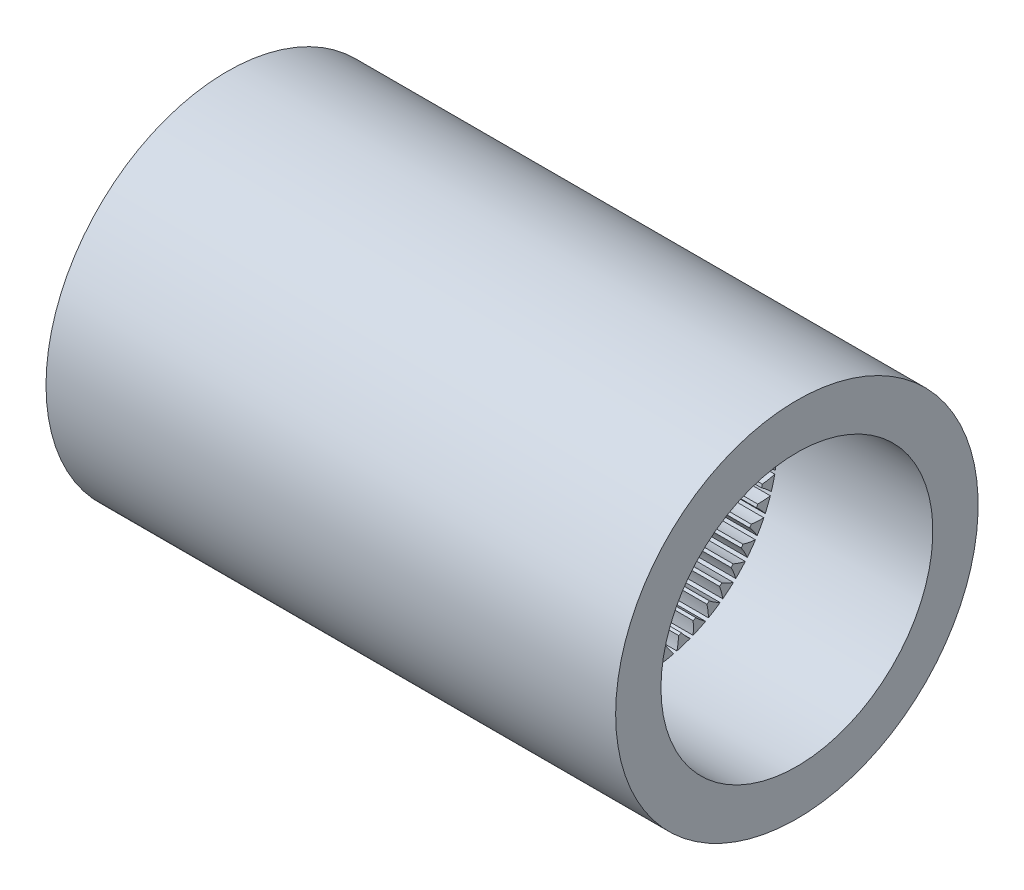
SolidWorks part; units mm, degrees
ref_plane "Plane1" through (0, 0, 0) normal (0, 0, 1) x (1, 0, 0)
ref_plane "Plane2" through (0, 0, 0) normal (0, 1, 0) x (1, 0, 0)
ref_plane "Plane3" through (0, 0, 0) normal (1, 0, 0) x (0, 0, -1)
other "Configuration Table"
sketch "HoldingSke" plane through (0, 0, 0) normal (0, 1, 0) x (1, 0, 0)
  line L0 (0, 0) -> (1.2856, -1.5321)
  line L1 (-15, 0) -> (100, 0) construction
  line L2 (0, 0) -> (-2.1039, 2.3779)
  line L3 (0, 0) -> (-11.863, 4.5341)
  line L4 (0, 0) -> (5.5511, 6.6156)
  line L5 (0, 0) -> (-23.7986, -8.8762)
  line L6 (0, 0) -> (-10.5278, -7.1032)
  line L7 (-2.1039, 2.3779) -> (3.3635, 27.1825)
  line L8 (-76.2, 2.8779) -> (-54.61, 2.8779)
  line L9 (-71.009, 38.7566) -> (-53.1078, 45.2721)
  line L10 (-76.2, 71.12) -> (104.1128, 71.12)
  line L11 (0, 0) -> (-15, 0)
  line L12 (-76.2, 101.6) -> (-76.181, 101.6)
  line L13 (24.9733, 27.94) -> (52.9518, 28.4284)
  line L14 (24.9733, 27.94) -> (24.9743, 27.94)
  line L15 (24.9733, 27.94) -> (100.4006, 29.5858)
  circle A0 centre (0, 0) radius 17.5
  circle A1 centre (0, 0) radius 12.7
  circle A2 centre (0, 0) radius 12.7
  dimension "Num_teeth" = 50
  dimension "Pitch_radius" = 180.3128
  dimension "Width" = 15
  dimension "Diameter" = 35
sketch "BasProSke" plane through (0, 0, 0) normal (0, 1, 0) x (1, 0, 0)
  line L0 (-10, 0) -> (60, 0) construction
  line L1 (0, 12) -> (0, 17.5)
  line L2 (0, 12) -> (15, 12)
  line L3 (15, 12) -> (15, 17.5)
  line L4 (15, 17.5) -> (0, 17.5)
  dimension "Thickness" = 15
  dimension "Diameter" = 35
revolve "Base-Revolve" add sketch "BasProSke" angle 360 about L0
sketch "TooCutSke" plane through (0, 0, 0) normal (1, 0, 0) x (0, 0, -1)
  line L3 (0.4401, 12.4922) -> (0.4401, 53.6633) construction
  line L4 (0, 0) -> (0, 59.563) construction
  line L5 (0, 0) -> (-4.2903, 68.1927) construction
  line L6 (-5.395, 10.253) -> (37.1043, 12.9269) construction
  circle A0 centre (0, 0) radius 12.5 construction
  circle A1 centre (0, 0) radius 13.126 construction
  circle A2 centre (0, 0) radius 10.5715 construction
  circle A3 centre (0, 0) radius 11.9746 construction
  arc A4 (0.6178, 11.9587) -> (0.1561, 13.1251) centre (-5.395, 10.253) ccw
  arc A5 (0.6178, 11.9587) -> (-0.6178, 11.9587) centre (0, 0) ccw
  arc A6 (0.1561, 13.1251) -> (-0.1561, 13.1251) centre (0, 0) ccw
  arc A7 (-0.1561, 13.1251) -> (-0.6178, 11.9587) centre (5.395, 10.253) ccw
extrude "ToothCut" cut sketch "TooCutSke" along normal through all
fillet "Breaks" [suppressed] radius 0.05
fillet "RootFillets" [suppressed] radius 0.126
pattern_circular "TeethCuts" count 50 every 7.2 about axis through (-10, 0, 0) along (1, 0, 0) of "RootFillets", "Breaks", "ToothCut"
sketch "Esquisse1" plane through (0, 0, 0) normal (-1, 0, 0) x (0, 0, 1)
  circle A0 centre (0, 0) radius 13.126
  circle A1 centre (0, 0) radius 17.5
  circle A2 centre (0, 0) radius 17.5
  arc A3 (9.0985, 9.4609) -> (8.871, 9.6746) centre (0, 0) ccw construction
  dimension "D1" = 0
extrude "Boss.-Extru.1" add sketch "Esquisse1" along normal blind 25 and the other way blind 30
equation "' \"Module@HoldingSke\" = 6.35"
equation "' \"Num_teeth@HoldingSke\" = 24"
equation "' \"Ap@HoldingSke\" =  14.5"
equation "' \"Ap@HoldingSke\" = 14.5"
equation "' \"Width@HoldingSke\" = 12"
equation "' \"Diameter@HoldingSke\" = 8 * 25.4"
equation "' \"Show_teeth@HoldingSke\" = 100"
equation "' \"Backlash@HoldingSke\" = 0.009 * 25.4"
equation "' \"Addendum_fac@HoldingSke\" = 1.0"
equation "' \"Dedendum_fac@HoldingSke\" = 1.25"
equation "' \"Dedendum_add@HoldingSke\" = 0.00005 * 25.4"
equation "' \"Clearance_fac@HoldingSke\" = 0.25"
equation "\"Pitch@HoldingSke\" = 1 / \"Module@HoldingSke\" "
equation "\"Overcut_dia@TooCutSke\" = (\"Num_teeth@HoldingSke\" - 2 * \"Addendum_fac@HoldingSke\") / \"Pitch@HoldingSke\" - 0.002 * 25.4"
equation "\"Pitch_dia@TooCutSke\" = \"Num_teeth@HoldingSke\" / \"Pitch@HoldingSke\""
equation "\"Base_dia@TooCutSke\" = \"Num_teeth@HoldingSke\" / \"Pitch@HoldingSke\" * cos((\"Ap@HoldingSke\"  * 3.14159265 / 180)) * 0.90"
equation "\"Root_dia@TooCutSke\" = \"Num_teeth@HoldingSke\"  / \"Pitch@HoldingSke\" + 2 *  \"Dedendum_fac@HoldingSke\"/ \"Pitch@HoldingSke\" + \"Dedendum_add@HoldingSke\" * 2"
equation "\"Half_ang@TooCutSke\" = 180 / \"Num_teeth@HoldingSke\""
equation "\"Half_CT@TooCutSke\" = \"Num_teeth@HoldingSke\" / \"Pitch@HoldingSke\" * sin((3.14159265 / 2 / \"Num_teeth@HoldingSke\")) / 2 + 10 * \"Backlash@HoldingSke\" / 4"
equation "\"Flank_rad@TooCutSke\" = \"Num_teeth@HoldingSke\" / \"Pitch@HoldingSke\" / 4"
equation "\"Radius@RootFillets\"= \"Clearance_fac@HoldingSke\" / \"Pitch@HoldingSke\" + \"Dedendum_add@HoldingSke\""
equation "\"Break_rad@Breaks\" = 0.02 / \"Pitch@HoldingSke\" * 5"
equation "\"Num_teeth@TeethCuts\" = int( \"Show_teeth@HoldingSke\" ) + 1"
equation "\"Num_teeth@TeethCuts\" = ((sgn( \"Num_teeth@TeethCuts\" - \"Num_teeth@HoldingSke\" )-1)*( \"Num_teeth@TeethCuts\" - \"Num_teeth@HoldingSke\" ))/-2+ \"Num_teeth@HoldingSke\""
equation "\"Num_teeth@TeethCuts\" = ((sgn( \"Num_teeth@TeethCuts\" - 2.0)+1)*( \"Num_teeth@TeethCuts\" - 2.0))/2 +2.0"
equation "\"Angle@TeethCuts\" = 360.0 / \"Num_teeth@HoldingSke\""
equation "\"Diameter@BasProSke\" = \"Num_teeth@HoldingSke\"  / \"Pitch@HoldingSke\" + 2 *  \"Dedendum_fac@HoldingSke\"/ \"Pitch@HoldingSke\" + \"Dedendum_add@HoldingSke\" * 2 + 0.002 * 25.4"
equation "\"Diameter@BasProSke\" = ((sgn( \"Diameter@BasProSke\"  - \"Diameter@HoldingSke\" )+1)*( \"Diameter@BasProSke\"  - \"Diameter@HoldingSke\" ))/2 + \"Diameter@HoldingSke\""
equation "\"Inside_diameter@BasProSke\" =  (\"Num_teeth@HoldingSke\" - 2 * \"Addendum_fac@HoldingSke\") / \"Pitch@HoldingSke\" "
equation "\"Thickness@BasProSke\"  = \"Width@HoldingSke\""
